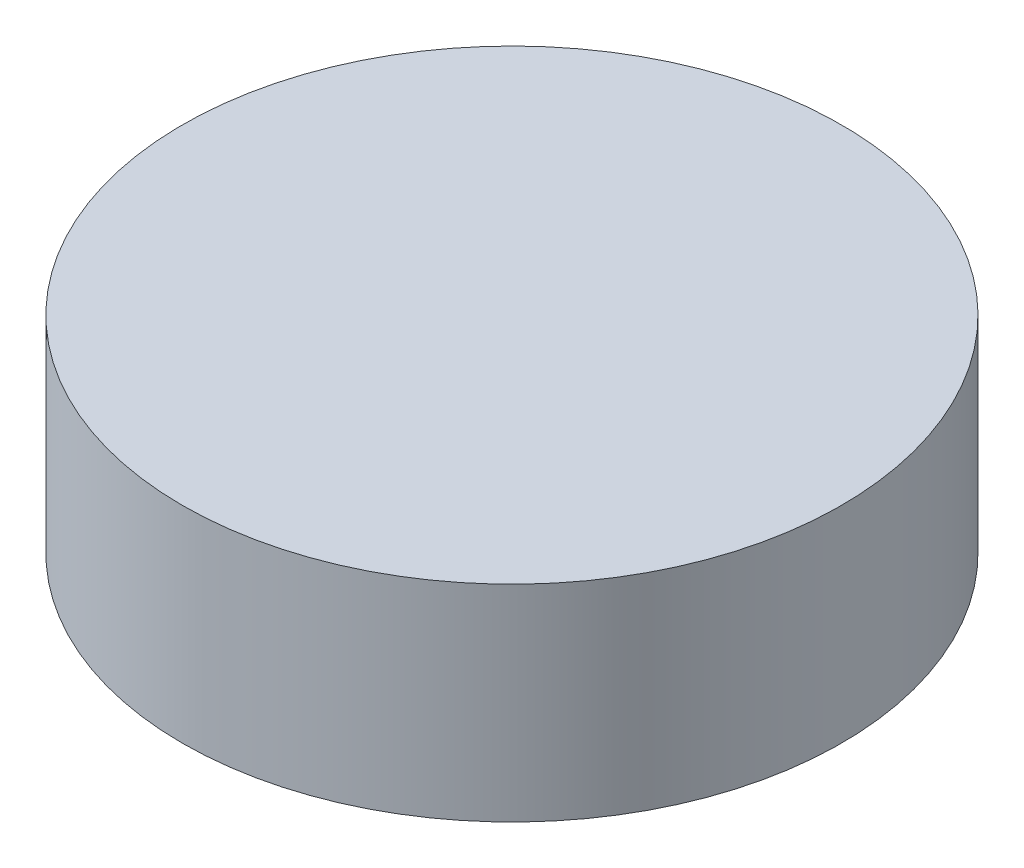
SolidWorks part; units mm, degrees
ref_plane "Front Plane" through (0, 0, 0) normal (0, 0, 1) x (1, 0, 0)
ref_plane "Top Plane" through (0, 0, 0) normal (0, 1, 0) x (1, 0, 0)
ref_plane "Right Plane" through (0, 0, 0) normal (1, 0, 0) x (0, 0, -1)
sketch "Sketch1" plane through (0, 0, 0) normal (0, 1, 0) x (1, 0, 0)
  circle A0 centre (0, 0) radius 40
extrude "Boss-Extrude1" add sketch "Sketch1" along normal blind 25
